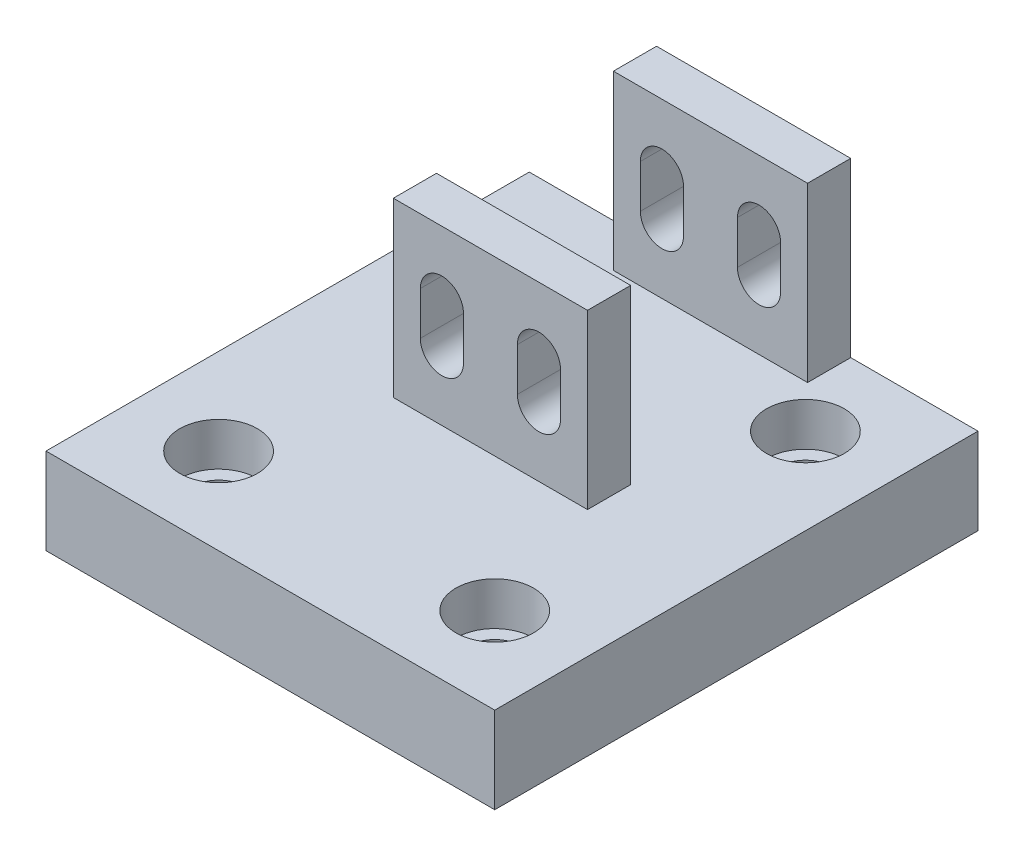
SolidWorks part; units mm, degrees
ref_plane "Front Plane" through (0, 0, 0) normal (0, 0, 1) x (1, 0, 0)
ref_plane "Top Plane" through (0, 0, 0) normal (0, 1, 0) x (1, 0, 0)
ref_plane "Right Plane" through (0, 0, 0) normal (1, 0, 0) x (0, 0, -1)
sketch "Sketch1" plane through (0, 0, 0) normal (0, 1, 0) x (1, 0, 0)
  line L0 (26, 0) -> (26, 51.7899) construction
  line L1 (0, 0) -> (52, 0)
  line L2 (0, 0) -> (0, 56)
  line L3 (0, 56) -> (52, 56)
  line L4 (52, 0) -> (52, 56)
  line L5 (10, 46) -> (42, 46) construction
  line L6 (10, 46) -> (10, 10) construction
  line L7 (10, 10) -> (42, 10) construction
  line L8 (42, 46) -> (42, 10) construction
  line L9 (54.3221, 28) -> (0, 28) construction
  circle A0 centre (10, 46) radius 2.95
  circle A1 centre (42, 46) radius 2.95
  circle A2 centre (42, 10) radius 2.95
  circle A3 centre (10, 10) radius 2.95
  dimension "D7" = 5.9
  dimension "D1" = 32
  dimension "D2" = 36
  dimension "D3" = 10
  dimension "D4" = 10
  dimension "D5" = 10
  dimension "D6" = 10
extrude "Boss-Extrude1" add sketch "Sketch1" along normal blind 10
sketch "Sketch2" plane through (0, 10, 0) normal (0, 1, 0) x (1, 0, 0)
  circle A0 centre (10, 10) radius 4.5
  circle A1 centre (42, 10) radius 4.5
  circle A2 centre (42, 46) radius 4.5
  circle A3 centre (10, 46) radius 4.5
  dimension "D1" = 9
extrude "Cut-Extrude1" cut sketch "Sketch2" against normal blind 5 and the other way through all
sketch "Sketch3" plane through (52, 0, 0) normal (1, 0, 0) x (0, 0, -1)
  line L0 (0, 10) -> (56, 10) construction
  line L1 (25.5, 10) -> (30.5, 10)
  line L2 (25.5, 10) -> (25.5, 30)
  line L3 (25.5, 30) -> (30.5, 30)
  line L4 (30.5, 10) -> (30.5, 30)
  line L5 (56, 10) -> (56, 0) construction
  line L6 (56, 10) -> (51, 10)
  line L7 (56, 10) -> (56, 30)
  line L8 (56, 30) -> (51, 30)
  line L9 (51, 10) -> (51, 30)
  dimension "D1" = 20.5
  dimension "D2" = 5
  dimension "D3" = 20
extrude "Boss-Extrude2" add sketch "Sketch3" against normal blind 22.5 from offset 14.75 offset against normal yes
sketch "Sketch4" plane through (0, 0, -25.5) normal (0, 0, 1) x (1, 0, 0)
  line L0 (20.375, 22.5) -> (20.375, 17.5) construction
  line L1 (22.875, 22.5) -> (22.875, 17.5)
  line L2 (17.875, 22.5) -> (17.875, 17.5)
  line L3 (31.625, 22.5) -> (31.625, 17.5) construction
  line L4 (34.125, 22.5) -> (34.125, 17.5)
  line L5 (29.125, 22.5) -> (29.125, 17.5)
  line L6 (14.75, 10) -> (37.25, 10) construction
  line L7 (26, 27.2126) -> (26, 33.0182) construction
  line L8 (14.75, 30) -> (37.25, 30) construction
  arc A0 (22.875, 22.5) -> (17.875, 22.5) centre (20.375, 22.5) ccw
  arc A1 (17.875, 17.5) -> (22.875, 17.5) centre (20.375, 17.5) ccw
  arc A2 (34.125, 22.5) -> (29.125, 22.5) centre (31.625, 22.5) ccw
  arc A3 (29.125, 17.5) -> (34.125, 17.5) centre (31.625, 17.5) ccw
  point P2 (20.375, 20)
  point P7 (31.625, 20)
  point P20 (26, 30)
  dimension "D1" = 5
  dimension "D2" = 5
  dimension "D3" = 10
  dimension "D4" = 5.625
extrude "Cut-Extrude2" cut sketch "Sketch4" against normal up to surface (30.5 mm away) up to face at (26, 12.5, -56)
